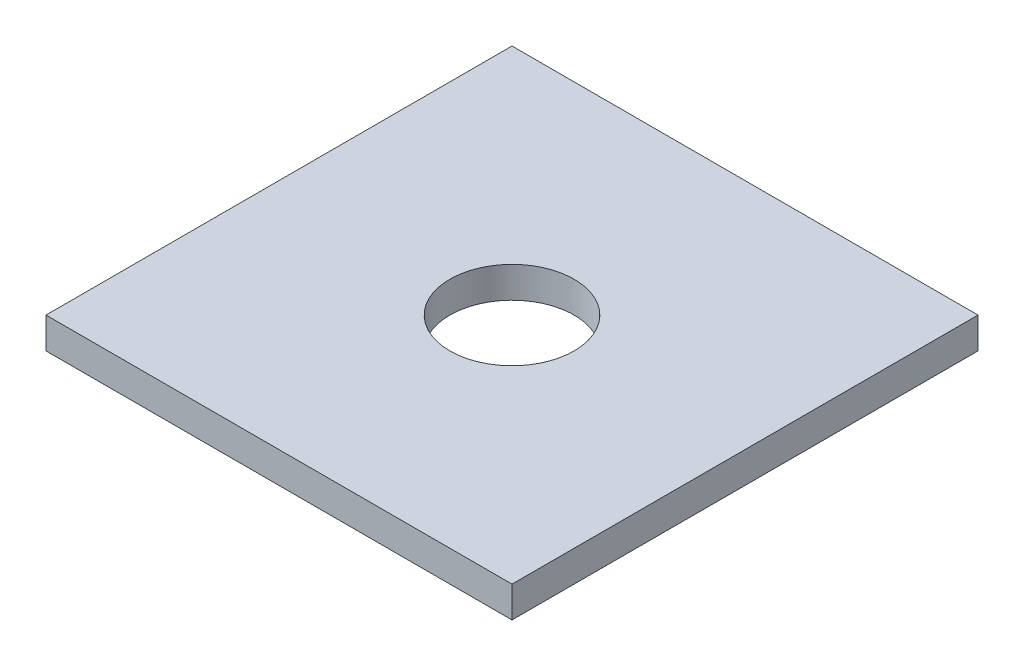
SolidWorks part; units mm, degrees
ref_plane "Front Plane" through (0, 0, 0) normal (0, 0, 1) x (1, 0, 0)
ref_plane "Top Plane" through (0, 0, 0) normal (0, 1, 0) x (1, 0, 0)
ref_plane "Right Plane" through (0, 0, 0) normal (1, 0, 0) x (0, 0, -1)
sketch "Sketch2" plane through (0, 0, 0) normal (0, 1, 0) x (1, 0, 0)
  line L1 (-75, -75) -> (75, -75)
  line L2 (-75, -75) -> (-75, 75)
  line L3 (-75, 75) -> (75, 75)
  line L4 (75, -75) -> (75, 75)
  line L5 (-75, -75) -> (75, 75) construction
  line L6 (-75, 75) -> (75, -75) construction
  circle A0 centre (0, 0) radius 20
  point P0 (0, 0)
  dimension "D2" = 40
  dimension "D1" = 150
extrude "Boss-Extrude3" add sketch "Sketch2" along normal blind 10
sketch "Sketch4" plane through (0, 10, 0) normal (0, 1, 0) x (1, 0, 0)
  line L7 (22.2049, 38.5873) -> (42.2049, 18.5873) construction
  line L8 (42.2049, 38.5873) -> (22.2049, 18.5873) construction
  line L9 (42.2049, 18.5873) -> (22.2049, 18.5873)
  line L10 (22.2049, 38.5873) -> (22.2049, 18.5873)
  line L11 (42.2049, 38.5873) -> (22.2049, 38.5873)
  line L12 (42.2049, 38.5873) -> (42.2049, 18.5873)
  line L15 (38.5873, -22.2049) -> (18.5873, -42.2049) construction
  line L16 (38.5873, -42.2049) -> (18.5873, -22.2049) construction
  line L17 (18.5873, -42.2049) -> (18.5873, -22.2049)
  line L18 (38.5873, -22.2049) -> (18.5873, -22.2049)
  line L19 (38.5873, -42.2049) -> (38.5873, -22.2049)
  line L20 (38.5873, -42.2049) -> (18.5873, -42.2049)
  point P13 (32.2049, 28.5873)
  point P20 (28.5873, -32.2049)
extrude "Cut-Extrude1" [suppressed] cut sketch "Sketch4" against normal blind 10
